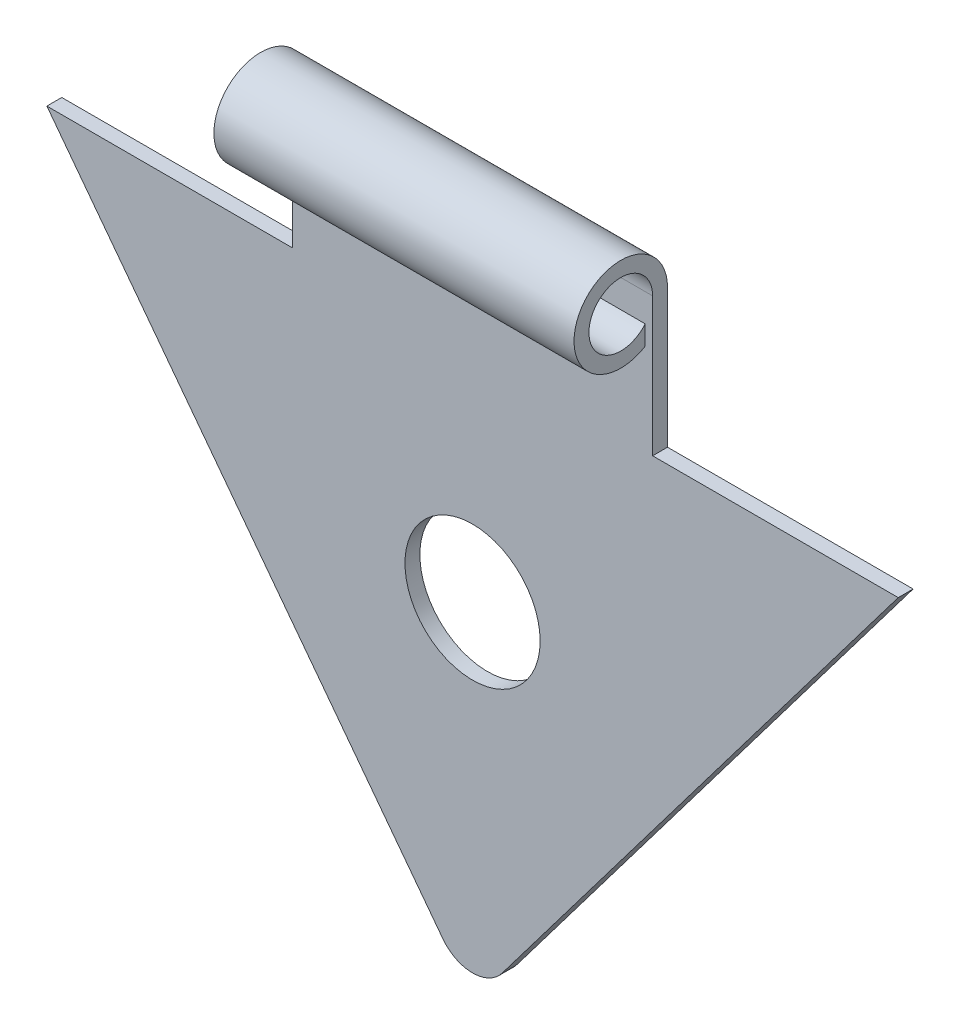
SolidWorks part; units mm, degrees
ref_plane "Front Plane" through (0, 0, 0) normal (0, 0, 1) x (1, 0, 0)
ref_plane "Top Plane" through (0, 0, 0) normal (0, 1, 0) x (1, 0, 0)
ref_plane "Right Plane" through (0, 0, 0) normal (1, 0, 0) x (0, 0, -1)
sketch "Sketch1" plane through (0, 0, 0) normal (0, 0, 1) x (1, 0, 0)
  line L0 (-11.43, 0) -> (11.43, 0)
  line L1 (0, 0) -> (0, -15.1) construction
  line L2 (-11.43, 0) -> (-0.7973, -14.0467)
  line L3 (0.7973, -14.0467) -> (11.43, 0)
  arc A0 (-0.7973, -14.0467) -> (0.7973, -14.0467) centre (0, -13.4431) ccw
  circle A1 centre (0, -5.82) radius 1.815
  point P4 (0, 0)
  dimension "D3" = 1
  dimension "D5" = 3.63
  dimension "D1" = 22.86
  dimension "D2" = 15.1
  dimension "D4" = 5.82
extrude "Boss-Extrude1" add sketch "Sketch1" along normal blind 0.4
sketch "Sketch3" plane through (0, 0, 0) normal (1, 0, 0) x (0, 0, -1)
  line L1 (-0.4, 0) -> (0, 0)
  line L9 (-0.4, 0) -> (0, 0) construction
  line L10 (0, 3.7187) -> (0, 0)
  line L11 (0, 3.7187) -> (-0.4, 3.7187) construction
  line L12 (-0.4, 3.7187) -> (-0.4, 0)
  line L13 (-0.6, 2.6482) -> (-0.6, 3.1691)
  arc A0 (0, 3.7187) -> (-0.6, 2.6482) centre (-1.255, 3.7187) ccw
  arc A1 (-0.4, 3.7187) -> (-0.6, 3.1691) centre (-1.255, 3.7187) ccw
  point P0 (-0.4, 0.0146)
  point P11 (-0.2, 0)
  point P12 (-0.2, 0)
  point P18 (0, 0)
  point P19 (0, 0)
  point P20 (0, 0)
  dimension "D2" = 2.51
  dimension "D3" = 0.2
  dimension "D1" = 3.7187
extrude "Boss-Extrude2" add sketch "Sketch3" along normal blind 4.835 and the other way blind 4.835
